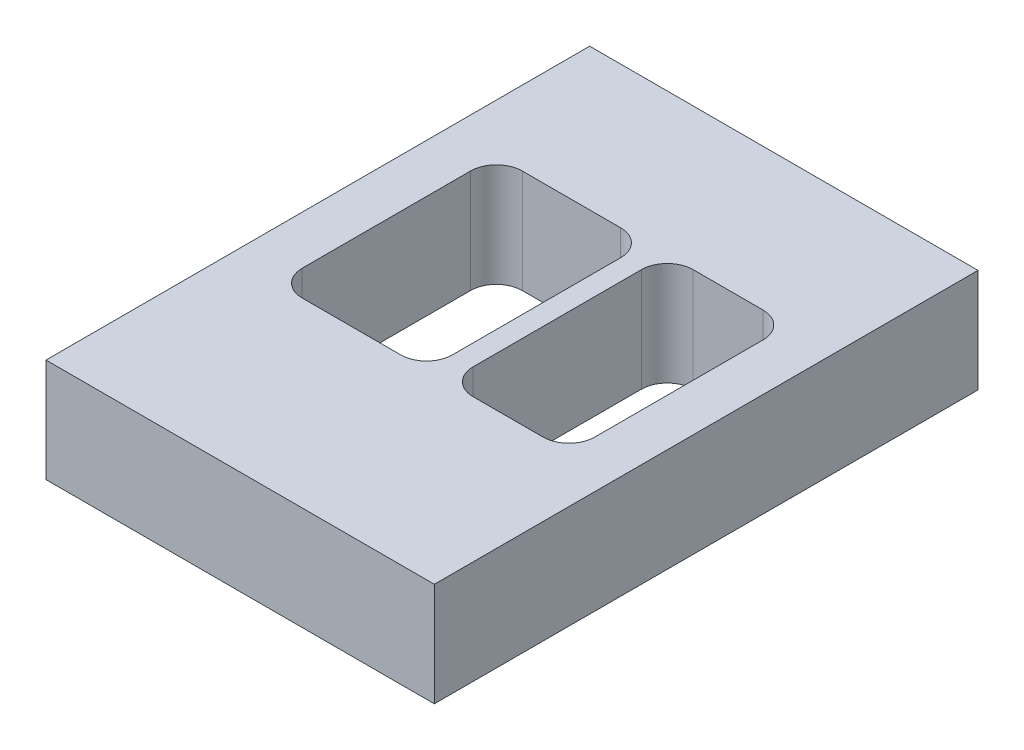
SolidWorks part; units mm, degrees
material "K110"
ref_plane "Front Plane" through (0, 0, 0) normal (0, 0, 1) x (1, 0, 0)
ref_plane "Top Plane" through (0, 0, 0) normal (0, 1, 0) x (1, 0, 0)
ref_plane "Right Plane" through (0, 0, 0) normal (1, 0, 0) x (0, 0, -1)
sketch "Sketch1" plane through (0, 0, 0) normal (0, 1, 0) x (1, 0, 0)
  line L1 (-75, 105) -> (75, 105)
  line L2 (-75, 105) -> (-75, -105)
  line L3 (-75, -105) -> (75, -105)
  line L4 (75, 105) -> (75, -105)
  line L5 (-75, 105) -> (75, -105) construction
  line L6 (-75, -105) -> (75, 105) construction
  point P0 (0, 0)
  dimension "D1" = 210
  dimension "D2" = 150
extrude "Boss-Extrude1" add sketch "Sketch1" against normal blind 40
sketch "Sketch2" plane through (0, 0, 0) normal (0, 1, 0) x (1, 0, 0)
  line L3 (24.75, -27.27) -> (24.75, -11.27) construction
  line L4 (27.75, -8.27) -> (33.88, -8.27) construction
  line L5 (35.88, -6.27) -> (35.88, 11.73) construction
  line L6 (33.88, 13.73) -> (27.75, 13.73) construction
  line L7 (24.75, 42.73) -> (24.75, 16.73) construction
  line L8 (-37.37, 42.73) -> (-13.25, 42.73) construction
  line L9 (-13.25, 42.73) -> (-13.25, 34.23) construction
  line L10 (-14.75, 32.73) -> (-29.37, 32.73) construction
  line L11 (-35.37, 26.73) -> (-35.37, -6.27) construction
  line L12 (-29.37, -12.27) -> (-14.75, -12.27) construction
  line L13 (-13.25, -27.27) -> (-13.25, -13.77) construction
  line L14 (-37.37, -27.27) -> (-13.25, -27.27) construction
  line L15 (-40.37, 39.73) -> (-40.37, -24.27) construction
  line L19 (24.75, -27.27) -> (24.75, -11.27)
  line L20 (27.75, -8.27) -> (33.88, -8.27)
  line L21 (35.88, -6.27) -> (35.88, 11.73)
  line L22 (33.88, 13.73) -> (27.75, 13.73)
  line L23 (24.75, 42.73) -> (24.75, 16.73)
  line L24 (-37.37, 42.73) -> (-13.25, 42.73)
  line L25 (-13.25, 42.73) -> (-13.25, 34.23)
  line L26 (-14.75, 32.73) -> (-29.37, 32.73)
  line L27 (-35.37, 26.73) -> (-35.37, -6.27)
  line L28 (-29.37, -12.27) -> (-14.75, -12.27)
  line L29 (-13.25, -27.27) -> (-13.25, -13.77)
  line L30 (-37.37, -27.27) -> (-13.25, -27.27)
  line L31 (-40.37, 39.73) -> (-40.37, -24.27)
  line L32 (40.88, 42.73) -> (40.88, 39.73) construction
  line L33 (37.88, 42.73) -> (40.88, 42.73) construction
  line L34 (40.88, -27.27) -> (37.88, -27.27) construction
  line L35 (40.88, -24.27) -> (40.88, -27.27) construction
  line L36 (24.75, 42.73) -> (37.88, 42.73) construction
  line L37 (40.88, 39.73) -> (40.88, -24.27) construction
  line L38 (37.88, -27.27) -> (24.75, -27.27) construction
  line L39 (24.75, 42.73) -> (37.88, 42.73)
  line L40 (40.88, 39.73) -> (40.88, -24.27)
  line L41 (37.88, -27.27) -> (24.75, -27.27)
  arc A0 (27.75, -8.27) -> (24.75, -11.27) centre (27.75, -11.27) ccw construction
  arc A1 (33.88, -8.27) -> (35.88, -6.27) centre (33.88, -6.27) ccw construction
  arc A2 (35.88, 11.73) -> (33.88, 13.73) centre (33.88, 11.73) ccw construction
  arc A3 (24.75, 16.73) -> (27.75, 13.73) centre (27.75, 16.73) ccw construction
  arc A4 (-37.37, 42.73) -> (-40.37, 39.73) centre (-37.37, 39.73) ccw construction
  arc A5 (-14.75, 32.73) -> (-13.25, 34.23) centre (-14.75, 34.23) ccw construction
  arc A6 (-29.37, 32.73) -> (-35.37, 26.73) centre (-29.37, 26.73) ccw construction
  arc A7 (-35.37, -6.27) -> (-29.37, -12.27) centre (-29.37, -6.27) ccw construction
  arc A8 (-13.25, -13.77) -> (-14.75, -12.27) centre (-14.75, -13.77) ccw construction
  arc A9 (-40.37, -24.27) -> (-37.37, -27.27) centre (-37.37, -24.27) ccw construction
  arc A10 (27.75, -8.27) -> (24.75, -11.27) centre (27.75, -11.27) ccw
  arc A11 (33.88, -8.27) -> (35.88, -6.27) centre (33.88, -6.27) ccw
  arc A12 (35.88, 11.73) -> (33.88, 13.73) centre (33.88, 11.73) ccw
  arc A13 (24.75, 16.73) -> (27.75, 13.73) centre (27.75, 16.73) ccw
  arc A14 (-37.37, 42.73) -> (-40.37, 39.73) centre (-37.37, 39.73) ccw
  arc A15 (-14.75, 32.73) -> (-13.25, 34.23) centre (-14.75, 34.23) ccw
  arc A16 (-29.37, 32.73) -> (-35.37, 26.73) centre (-29.37, 26.73) ccw
  arc A17 (-35.37, -6.27) -> (-29.37, -12.27) centre (-29.37, -6.27) ccw
  arc A18 (-13.25, -13.77) -> (-14.75, -12.27) centre (-14.75, -13.77) ccw
  arc A19 (-40.37, -24.27) -> (-37.37, -27.27) centre (-37.37, -24.27) ccw
  arc A20 (40.88, 39.73) -> (37.88, 42.73) centre (37.88, 39.73) ccw construction
  arc A21 (37.88, -27.27) -> (40.88, -24.27) centre (37.88, -24.27) ccw construction
  arc A22 (40.88, 39.73) -> (37.88, 42.73) centre (37.88, 39.73) ccw
  arc A23 (37.88, -27.27) -> (40.88, -24.27) centre (37.88, -24.27) ccw
sketch "Sketch3" plane through (0, 0, 0) normal (0, 1, 0) x (1, 0, 0)
  line L1 (-56.25, 50.23) -> (1.75, 50.23)
  line L2 (-56.25, 50.23) -> (-56.25, -34.77)
  line L3 (-56.25, -34.77) -> (1.75, -34.77)
  line L4 (1.75, 50.23) -> (1.75, -34.77)
  line L5 (9.75, 50.23) -> (56.75, 50.23)
  line L6 (9.75, 50.23) -> (9.75, -34.77)
  line L7 (9.75, -34.77) -> (56.75, -34.77)
  line L8 (56.75, 50.23) -> (56.75, -34.77)
  line L15 (24.75, 42.73) -> (24.75, 16.73) construction
  line L16 (-13.25, 42.73) -> (-13.25, 34.23) construction
  dimension "D1" = 85
  dimension "D4" = 15
  dimension "D5" = 15
  dimension "D6" = 47
  dimension "D7" = 58
extrude "Cut-Extrude1" cut sketch "Sketch3" against normal up to next
fillet "Fillet1" radius 10 8 edges at (9.75, -20, -50.23) (56.75, -20, 34.77) (56.75, -20, -50.23) (9.75, -20, 34.77) (-56.25, -20, 34.77) (1.75, -20, 34.77) (1.75, -20, -50.23) (-56.25, -20, -50.23)
